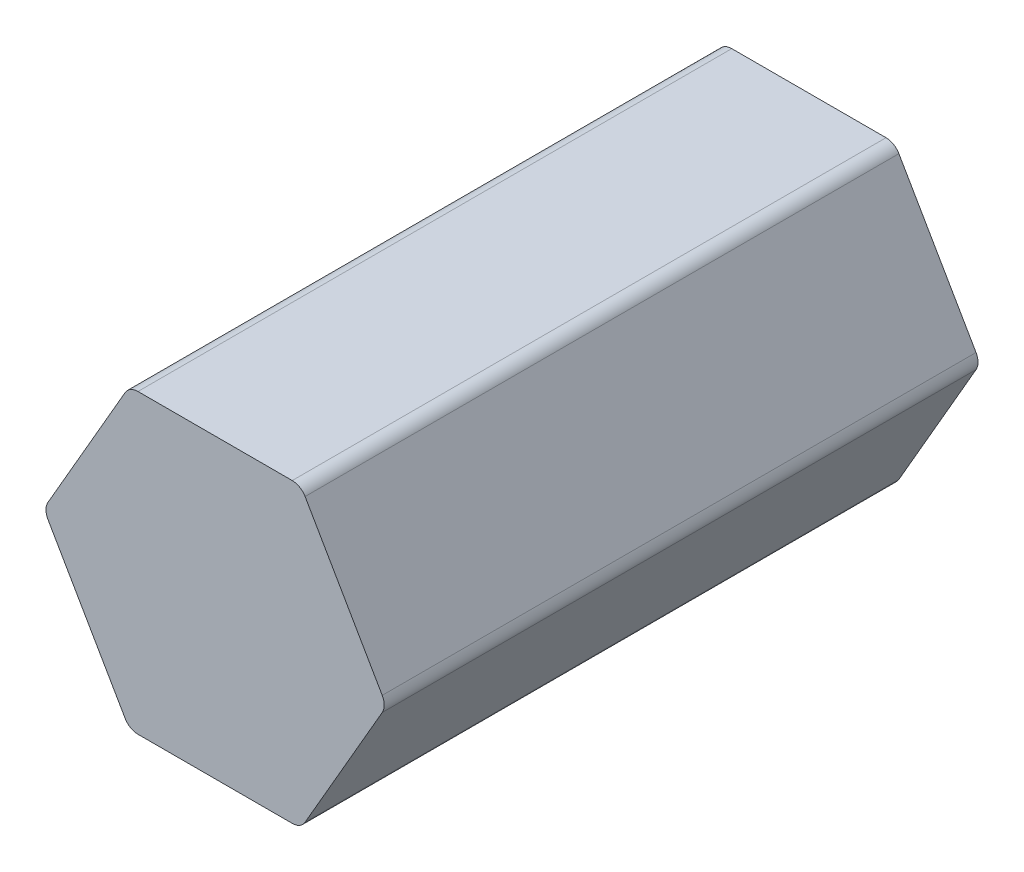
SolidWorks part; units mm, degrees
material "AISI 1020 Steel, Cold Rolled"
ref_plane "Front Plane" through (0, 0, 0) normal (0, 0, 1) x (1, 0, 0)
ref_plane "Top Plane" through (0, 0, 0) normal (0, 1, 0) x (1, 0, 0)
ref_plane "Right Plane" through (0, 0, 0) normal (1, 0, 0) x (0, 0, -1)
other "Configuration Table"
sketch "Sketch1" plane through (0, 0, 0) normal (0, 0, 1) x (1, 0, 0)
  line L1 (7.3323, 0) -> (3.6662, 6.35)
  line L2 (3.6662, 6.35) -> (-3.6662, 6.35)
  line L3 (-3.6662, 6.35) -> (-7.3323, 0)
  line L4 (-7.3323, 0) -> (-3.6662, -6.35)
  line L5 (-3.6662, -6.35) -> (3.6662, -6.35)
  line L6 (3.6662, -6.35) -> (7.3323, 0)
  circle A0 centre (0, 0) radius 6.35 construction
  dimension "D1" = 12.7
extrude "Boss-Extrude1" add sketch "Sketch1" along normal mid plane 25.4
fillet "Fillet1" radius 0.635 6 edges at (3.6662, -6.35, 0) (-3.6662, -6.35, 0) (-7.3323, 0, 0) (-3.6662, 6.35, 0) (7.3323, 0, 0) (3.6662, 6.35, 0)
equation "\"length\"= 1"
equation "\"D1@Boss-Extrude1\"=\"length\""
